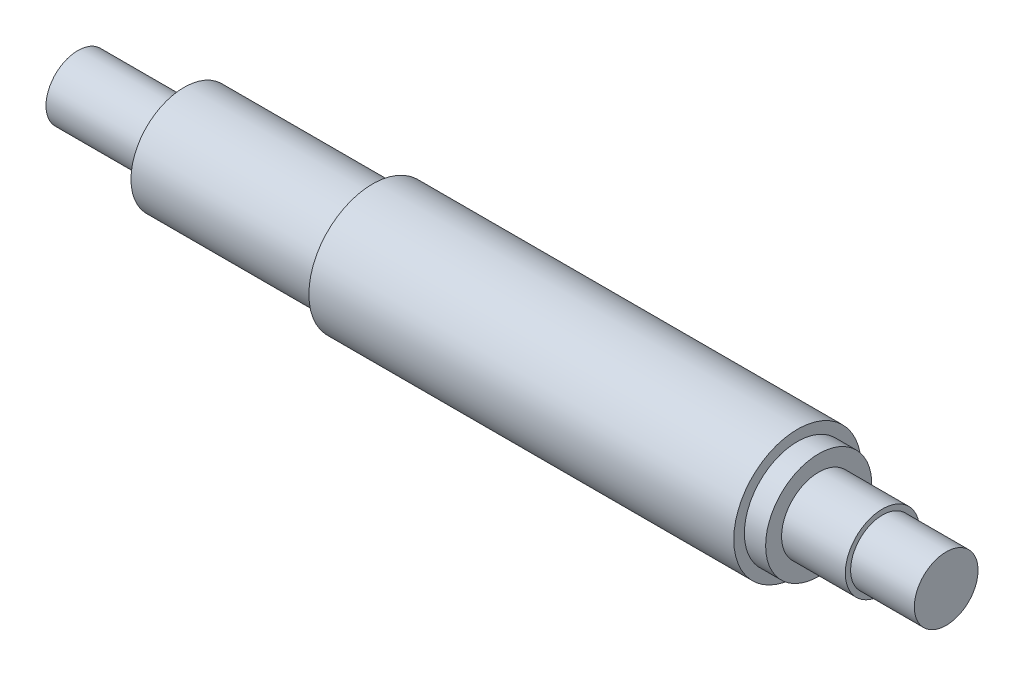
SolidWorks part; units mm, degrees
ref_plane "Front Plane" through (0, 0, 0) normal (0, 0, 1) x (1, 0, 0)
ref_plane "Top Plane" through (0, 0, 0) normal (0, 1, 0) x (1, 0, 0)
ref_plane "Right Plane" through (0, 0, 0) normal (1, 0, 0) x (0, 0, -1)
sketch "Sketch2" plane through (0, 0, 0) normal (0, 0, 1) x (1, 0, 0)
  line L0 (-40.875, 0) -> (40.875, 0)
  line L1 (-40.875, 0) -> (-40.875, 3)
  line L2 (-40.875, 3) -> (-30.875, 3)
  line L3 (-13.125, 5) -> (-13.125, 6)
  line L4 (-13.125, 6) -> (26.875, 6)
  line L5 (26.875, 6) -> (26.875, 5)
  line L6 (-30.875, 3) -> (-30.875, 5)
  line L7 (-30.875, 5) -> (-13.125, 5)
  line L8 (26.875, 5) -> (28.875, 5)
  line L9 (28.875, 5) -> (28.875, 3.5)
  line L10 (28.875, 3.5) -> (34.875, 3.5)
  line L11 (34.875, 3.5) -> (34.875, 3)
  line L13 (34.875, 3) -> (40.875, 3)
  line L14 (40.875, 3) -> (40.875, 0)
  point P5 (0, 0)
  dimension "D2" = 6
  dimension "D3" = 3
  dimension "D4" = 10
  dimension "D5" = 27.75
  dimension "D6" = 40
  dimension "D7" = 6
  dimension "D8" = 2
  dimension "D9" = 5
  dimension "D11" = 5
  dimension "D12" = 6
  dimension "D10" = 3.5
  dimension "D13" = 3
revolve "Revolve1" add sketch "Sketch2" angle 360 about L0
sketch "Sketch3" [suppressed] plane through (0, 0, 0) normal (0, 0, 1) x (1, 0, 0)
  line L0 (-43.375, 0) -> (43.375, 0)
  line L1 (-43.375, 0) -> (-43.375, 3)
  line L2 (-43.375, 3) -> (-33.375, 3)
  line L3 (-20.625, 5) -> (-20.625, 7.5)
  line L4 (-20.625, 7.5) -> (29.375, 7.5)
  line L5 (29.375, 7.5) -> (29.375, 5)
  line L6 (-33.375, 3) -> (-33.375, 5)
  line L7 (-33.375, 5) -> (-20.625, 5)
  line L8 (29.375, 5) -> (31.375, 5)
  line L9 (31.375, 5) -> (31.375, 3.5)
  line L10 (31.375, 3.5) -> (37.375, 3.5)
  line L11 (43.375, 3) -> (43.375, 0)
  line L13 (4.375, 7.5) -> (4.375, 16.7852) construction
  line L14 (37.375, 3.5) -> (37.375, 3)
  line L15 (37.375, 3) -> (43.375, 3)
  point P4 (0, 0)
  point P17 (29.375, 6.25)
  dimension "D12" = 6
  dimension "D2" = 7.5
  dimension "D4" = 3
  dimension "D1" = 10
  dimension "D8" = 5
  dimension "D10" = 5
  dimension "D3" = 50
  dimension "D5" = 22.75
  dimension "D7" = 2
  dimension "D6" = 3.5
  dimension "D9" = 3
  dimension "D11" = 6
revolve "Revolve2" [suppressed] add sketch "Sketch3" angle 360 about L0
equation "\"mini-flipper-shaft-diameter\"= 26mm"
equation "\"mini-shaft-ring-groove-diam\"= 7.8mm"
equation "\"mini-shaft-ring-groove-width\"= 1mm"
equation "\"dtCoverPlate-DistFrom-GearCent\"= 73mm"
equation "\"wormGearShaft-L\"= \"dtCoverPlate-DistFrom-GearCent\" - 27.75 + 3.75"
equation "\"wormGearShaft-Dsmall\"= 6mm"
equation "\"wormGearShaft-Dworm\"= 12mm"
equation "\"D3@Sketch2\"=\"wormGearShaft-Dsmall\"/2"
equation "\"D4@Sketch3\"=\"wormGearShaft-Dsmall\"/2"
equation "\"wormL-D\" = 12mm"
equation "\"wormR-D\" = 15mm"
equation "\"wormGearL-D\" = 40mm"
equation "\"wormGearR-D\" = 50mm"
equation "\"D5@Sketch3\"=73-\"wormGearR-D\"/2 - 17.25-8"
equation "\"D5@Sketch2\"=73-\"wormGearL-D\"/2 -17.25-8"
